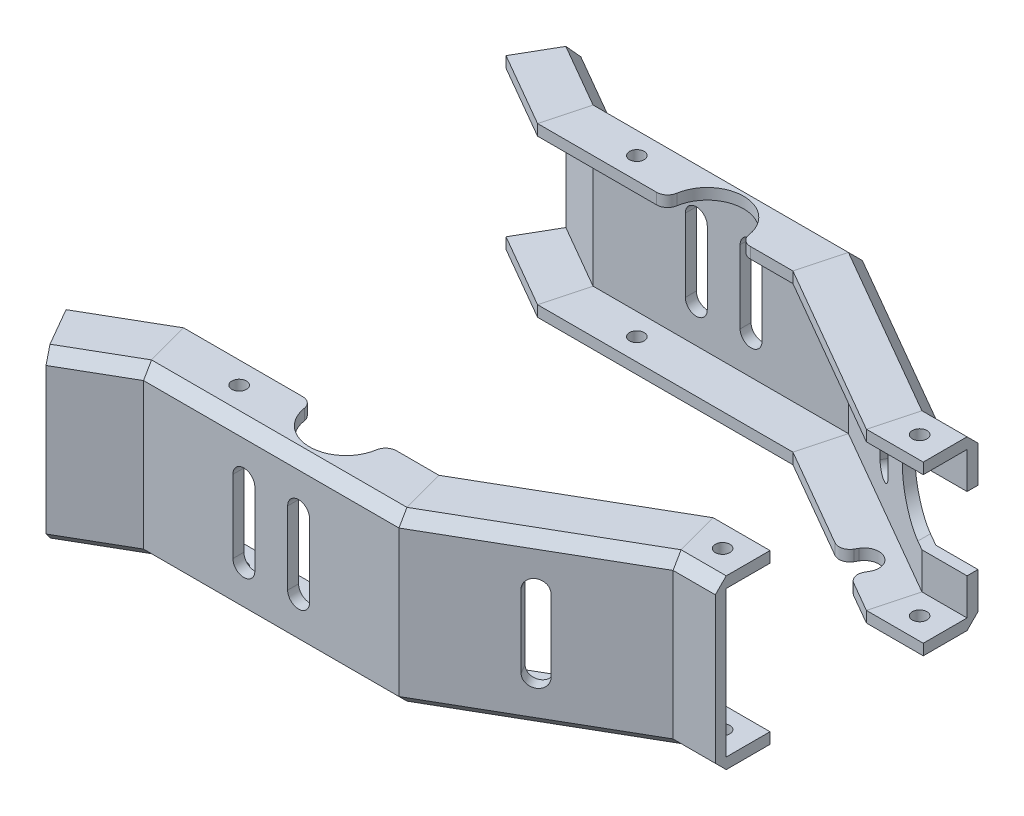
SolidWorks part; units mm, degrees
material "ABS PC"
ref_plane "Front Plane" through (0, 0, 0) normal (0, 0, 1) x (1, 0, 0)
ref_plane "Top Plane" through (0, 0, 0) normal (0, 1, 0) x (1, 0, 0)
ref_plane "Right Plane" through (0, 0, 0) normal (1, 0, 0) x (0, 0, -1)
sketch "Sketch6" plane through (0, 0, 0) normal (0, 1, 0) x (1, 0, 0)
  line L0 (0, 0) -> (-70, 0)
  line L1 (-70, 0) -> (-87.3205, -10)
  line L2 (0, 0) -> (47.6314, 27.5)
  line L3 (47.6314, 27.5) -> (59.6314, 27.5)
  dimension "D1" = 70
  dimension "D2" = 20
  dimension "D3" = 150
  dimension "D4" = 55
  dimension "D5" = 12
ref_plane "Plane5" through (0, 0, 0) normal (1, 0, 0) x (0, 0, -1)
sketch "Sketch7" plane through (0, 0, 0) normal (1, 0, 0) x (0, 0, -1)
  line L0 (1.3953, 0) -> (11.0315, 0) construction
  line L2 (-1.6047, -23) -> (-1.6047, 23)
  line L4 (1.3953, -20) -> (1.3953, 20)
  line L5 (-1.6047, -23) -> (1.3953, 20) construction
  line L6 (-1.6047, 23) -> (1.3953, -20) construction
  line L7 (13.3953, 20) -> (13.3953, 23)
  line L8 (1.3953, -20) -> (13.3953, -20)
  line L10 (-1.6047, -23) -> (13.3953, -23)
  line L11 (13.3953, -20) -> (13.3953, -23)
  line L12 (-1.6047, 23) -> (13.3953, 23)
  line L14 (1.3953, 20) -> (13.3953, 20)
  point P0 (0, 0)
  dimension "D1" = 3
  dimension "D3" = 3
  dimension "D2" = 40
  dimension "D5" = 15
sweep "Sweep8" add profiles "Sketch7" path "Sketch6"
ref_plane "Plane6" through (0, 0, -61.8953) normal (0, 0, -1) x (-1, 0, 0)
sketch "Sketch8" plane through (0, 23, 0) normal (0, 1, 0) x (1, 0, 0)
  line L1 (-73.5893, 13.3953) -> (-94.0182, 1.6007) construction
  line L3 (-89.0182, -7.0595) -> (-94.0182, 1.6007)
  line L4 (-94.0182, 1.6007) -> (-81.0278, 9.1007)
  line L5 (-94.0182, 1.6007) -> (-86.5182, -11.3897) construction
  line L6 (-81.0278, 9.1007) -> (-89.0182, -7.0595)
  dimension "D1" = 15
  dimension "D2" = 10
extrude "Cut-Extrude1" [suppressed] cut sketch "Sketch8" against normal through all
sketch "Sketch9" plane through (0, 23, 0) normal (0, 1, 0) x (1, 0, 0)
  line L0 (-73.5893, 13.3953) -> (-94.0182, 1.6007) construction
  line L1 (-94.0182, 1.6007) -> (-86.5182, -11.3897) construction
  line L2 (-83.6259, 7.6007) -> (-94.0182, 1.6007)
  line L3 (-94.0182, 1.6007) -> (-89.5182, -6.1935)
  line L4 (-89.5182, -6.1935) -> (-86.9201, -4.6935)
  line L5 (-83.6259, 7.6007) -> (-79.1259, -0.1935) construction
  line L6 (-79.1259, -0.1935) -> (-86.9201, -4.6935) construction
  arc A1 (-83.6259, 7.6007) -> (-86.9201, -4.6935) centre (-91.4201, 3.1007) cw
  dimension "D1" = 12
  dimension "D2" = 9
extrude "Cut-Extrude2" [suppressed] cut sketch "Sketch9" against normal through all
sketch "Sketch10" plane through (0, 23, 0) normal (0, 1, 0) x (1, 0, 0)
  line L0 (-3.5893, 13.3953) -> (-73.5893, 13.3953) construction
  line L1 (-38.0893, 13.3953) -> (-18.0893, 13.3953)
  line L2 (-38.0893, 13.3953) -> (-38.0893, 12.3953)
  line L3 (-38.0893, 12.3953) -> (-18.0893, 12.3953) construction
  line L4 (-18.0893, 13.3953) -> (-18.0893, 12.3953)
  arc A0 (-38.0893, 12.3953) -> (-18.0893, 12.3953) centre (-28.0893, 12.3953) ccw
  dimension "D1" = 1
  dimension "D2" = 20
  dimension "D3" = 24.5
extrude "Cut-Extrude3" cut sketch "Sketch10" against normal blind 5
sketch "Sketch11" plane through (0, 0, 1.6047) normal (0, 0, 1) x (1, 0, 0)
  line L0 (-34.57, 23) -> (-34.57, -23) construction
  line L3 (-42.07, -10) -> (-42.07, 10) construction
  line L4 (-45.07, -10) -> (-45.07, 10)
  line L5 (-39.07, -10) -> (-39.07, 10)
  line L6 (-27.07, -10) -> (-27.07, 10) construction
  line L7 (-24.07, -10) -> (-24.07, 10)
  line L8 (-30.07, -10) -> (-30.07, 10)
  line L9 (-34.57, 0) -> (-42.07, 0) construction
  line L10 (0.43, 23) -> (-69.57, 23) construction
  line L11 (0.43, -23) -> (-69.57, -23) construction
  arc A0 (-45.07, -10) -> (-39.07, -10) centre (-42.07, -10) ccw
  arc A1 (-39.07, 10) -> (-45.07, 10) centre (-42.07, 10) ccw
  arc A2 (-24.07, -10) -> (-30.07, -10) centre (-27.07, -10) cw
  arc A3 (-30.07, 10) -> (-24.07, 10) centre (-27.07, 10) cw
  point P8 (-42.07, 0)
  point P15 (-27.07, 0)
  dimension "D1" = 15
  dimension "D2" = 6
  dimension "D3" = 20
extrude "Cut-Extrude4" cut sketch "Sketch11" against normal blind 10
chamfer "Chamfer1" distance 3 angle 45 8 edges at (-78.0441, -23, 6.4972) (-34.57, -23, 1.6047) (24.2457, -23, -12.1453) (-78.0441, 23, 6.4972) (-34.57, 23, 1.6047) (24.2457, 23, -12.1453) (53.8464, -23, -25.8953) (53.8464, 23, -25.8953)
sketch "Sketch14" plane through (0.8023, 0, 1.3897) normal (0.5, 0, 0.866) x (0.866, 0, -0.5)
  line L0 (27.07, -10) -> (27.07, 10) construction
  line L1 (24.07, -10) -> (24.07, 10)
  line L2 (30.07, -10) -> (30.07, 10)
  line L3 (27.07, -20) -> (27.07, -10) construction
  line L5 (0, 0) -> (27.07, 0) construction
  line L6 (-0.43, -20) -> (54.57, -20) construction
  arc A0 (24.07, -10) -> (30.07, -10) centre (27.07, -10) ccw
  arc A1 (30.07, 10) -> (24.07, 10) centre (27.07, 10) ccw
  point P2 (27.07, 0)
  dimension "D1" = 20
  dimension "D2" = 6
extrude "Cut-Extrude6" cut sketch "Sketch14" against normal blind 3
hole_wizard "Ø4.0mm Dowel Hole2" positions "Sketch18" profile "Sketch19" hole size "Ø4.0" standard "ANSI Metric" end condition through all
sketch "Sketch18" plane through (0, -23, 0) normal (0, -1, 0) x (-1, 0, 0)
  line L6 (-52.6314, 34.8953) -> (-52.6314, 28.8953) construction
  line L7 (-59.6314, 28.8953) -> (-47.2575, 28.8953) construction
  line L11 (52.3686, 7.3953) -> (52.3686, 1.3953) construction
  line L12 (0.3739, 1.3953) -> (70.3739, 1.3953) construction
  line L14 (-59.6314, 28.8953) -> (-59.6314, 40.8953) construction
  point P0 (52.3686, 7.3953)
  point P2 (-52.6314, 34.8953)
  dimension "D1" = 6
  dimension "D2" = 105
  dimension "D3" = 7
sketch "Sketch19" plane through (-52.3686, -23, -7.3953) normal (1, 0, 0) x (0, 0, -1)
  line L0 (0, 0) -> (0, 46)
  line L1 (0, 46) -> (2, 46)
  line L2 (2, 46) -> (2, 0)
  line L5 (2, 0) -> (0, 0)
  line L11 (0, -6.35) -> (0, 107.95) construction
  dimension "Thru Hole Dia." = 4
  dimension "Thru Hole Depth" = 46
sketch "Sketch22" plane through (0, -23, 0) normal (0, -1, 0) x (1, 0, 0)
  line L0 (26.2886, -30.6453) -> (33.2168, -34.6453)
  line L1 (26.2886, -30.6453) -> (28.2886, -27.1812)
  line L2 (33.2168, -34.6453) -> (35.2168, -31.1812)
  line L3 (28.2886, -27.1812) -> (35.2168, -31.1812)
  line L4 (44.0421, -40.8953) -> (-3.5893, -13.3953) construction
  arc A0 (28.2886, -27.1812) -> (35.2168, -31.1812) centre (31.7527, -29.1812) cw
  line M7 (-3.5893, -13.3953) -> (44.0421, -40.8953)
  dimension "D1" = 4
  dimension "D2" = 8
  dimension "D3" = 12.5
extrude "Cut-Extrude9" cut sketch "Sketch22" against normal blind 10 contours A0 L3 | L3 L1 L2 M7 region at (30.7527, -23, -30.9133) region at (32.6015, -23, -27.711)
mirror "Mirror2" about plane through (0, 0, -61.8953) normal (0, 0, -1) of bodies 116 103
sketch "Sketch20" plane through (0, 0, -97.8953) normal (0, 0, -1) x (-1, 0, 0)
  line L0 (-59.6314, 0) -> (-52.1314, 0) construction
  line L1 (-59.6314, 20) -> (-59.6314, -20) construction
  line L3 (-44.6314, -10) -> (-59.6314, -10)
  line L4 (-44.6314, -10) -> (-44.6314, 10)
  line L5 (-44.6314, 10) -> (-59.6314, 10)
  line L6 (-59.6314, -10) -> (-59.6314, 10)
  line L7 (-44.6314, -10) -> (-59.6314, 10) construction
  line L8 (-44.6314, 10) -> (-59.6314, -10) construction
  arc A0 (-44.6314, 10) -> (-44.6314, -10) centre (-44.6314, 0) cw
  point P5 (-52.1314, 0)
  line M3 (-48.0614, -20) -> (-48.0614, 20)
  line M5 (-59.6314, 20) -> (-59.6314, -20)
  dimension "D1" = 20
  dimension "D2" = 15
extrude "Cut-Extrude7" cut sketch "Sketch20" against normal blind 5 and the other way through all contours A0 L4 | L5 L3 M3 M5 | L4 L5 L3 M3 region at (46.3464, 0, -97.8953) region at (40.3873, 0, -97.8953) region at (53.8464, 0, -97.8953)
sketch "Sketch21" plane through (0, 0, -25.8953) normal (0, 0, 1) x (1, 0, 0)
  line L0 (59.6314, 0) -> (54.6314, 0) construction
  line L2 (59.6314, 20) -> (59.6314, -20) construction
  line L3 (59.6314, -7.5) -> (49.6314, -7.5)
  line L4 (59.6314, -7.5) -> (59.6314, 7.5)
  line L5 (59.6314, 7.5) -> (49.6314, 7.5)
  line L6 (49.6314, -7.5) -> (49.6314, 7.5)
  line L7 (59.6314, -7.5) -> (49.6314, 7.5) construction
  line L8 (59.6314, 7.5) -> (49.6314, -7.5) construction
  arc A0 (49.6314, 7.5) -> (49.6314, -7.5) centre (49.6314, 0) ccw
  point P5 (54.6314, 0)
  line M14 (48.0614, 20) -> (48.0614, -20)
  line M16 (59.6314, -20) -> (59.6314, 20)
  dimension "D1" = 15
  dimension "D2" = 10
extrude "Cut-Extrude8" [suppressed] cut sketch "Sketch21" against normal blind 10 and the other way blind 10 contours A0 M14 | L6 A0 M14 | L6 L3 L5 M16
fillet "Fillet1" radius 3 4 edges at (26.2886, -21.5, -30.6453) (33.2168, -21.5, -34.6453) (-18.0893, 21.5, -13.3953) (-38.0893, 21.5, -13.3953)
fillet "Fillet2" radius 3 4 edges at (-38.0893, 21.5, -110.3953) (-18.0893, 21.5, -110.3953) (26.2886, -21.5, -93.1453) (33.2168, -21.5, -89.1453)
